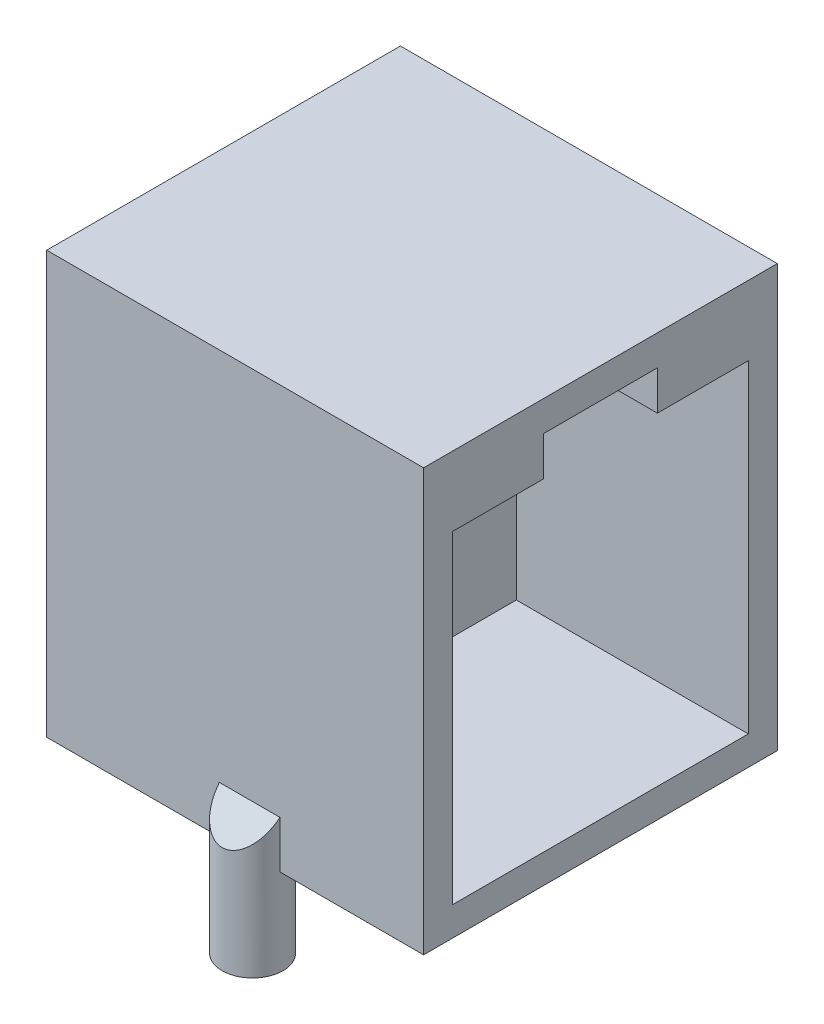
SolidWorks part; units mm, degrees
ref_plane "Front Plane" through (0, 0, 0) normal (0, 0, 1) x (1, 0, 0)
ref_plane "Top Plane" through (0, 0, 0) normal (0, 1, 0) x (1, 0, 0)
ref_plane "Right Plane" through (0, 0, 0) normal (1, 0, 0) x (0, 0, -1)
sketch "Sketch1" plane through (0, 0, 0) normal (0, 1, 0) x (1, 0, 0)
  line L1 (0, 0) -> (13, 0)
  line L2 (0, 0) -> (0, 12.2)
  line L3 (0, 12.2) -> (13, 12.2)
  line L4 (13, 0) -> (13, 12.2)
  dimension "D1" = 13
  dimension "D2" = 12.2
extrude "Boss-Extrude1" add sketch "Sketch1" along normal blind 14.55
sketch "Sketch2" plane through (0, 0, 0) normal (0, -1, 0) x (1, 0, 0)
  line L0 (7, 0) -> (7, -12.2) construction
  line L1 (0, 0) -> (13, 0) construction
  line L2 (13, -12.2) -> (0, -12.2) construction
  line L3 (7, -12.1) -> (7, -0.1) construction
  line L4 (13, 0) -> (13, -12.2) construction
  circle A0 centre (7, -0.1) radius 1.05
  circle A1 centre (7, -12.1) radius 1.05
  point P10 (7, -6.1)
  point P13 (7, -6.1)
  dimension "D1" = 2.1
  dimension "D2" = 12
  dimension "D3" = 6
extrude "Boss-Extrude2" add sketch "Sketch2" along normal blind 3
sketch "Sketch3" plane through (13, 0, 0) normal (1, 0, 0) x (0, 0, -1)
  line L2 (1.0003, 12.1496) -> (1.0003, 1.0003)
  line L4 (11.1997, 1.0003) -> (11.1997, 12.1496)
  line L8 (1.0003, 1.0003) -> (0, 1.0003) construction
  line L9 (0, 14.55) -> (0, 0) construction
  line L10 (11.1997, 1.0003) -> (12.2, 1.0003) construction
  line L11 (12.2, 14.55) -> (12.2, 0) construction
  line L12 (5.3043, 1.0003) -> (5.3043, 0) construction
  line L13 (0, 0) -> (12.2, 0) construction
  line L14 (1.0003, 1.0003) -> (11.1997, 1.0003)
  line L20 (1.0003, 12.1496) -> (4.1349, 12.1496)
  line L21 (4.1349, 12.1496) -> (4.1349, 13.5035)
  line L22 (4.1349, 13.5035) -> (8.0651, 13.5035)
  line L23 (8.0651, 13.5035) -> (8.0651, 12.1496)
  line L24 (8.0651, 12.1496) -> (11.1997, 12.1496)
extrude "Cut-Extrude1" cut sketch "Sketch3" against normal blind 8
chamfer "Chamfer1" distance 1.63 angle 45 2 edges at (7, 0, 0) (7, 0, -12.2)
